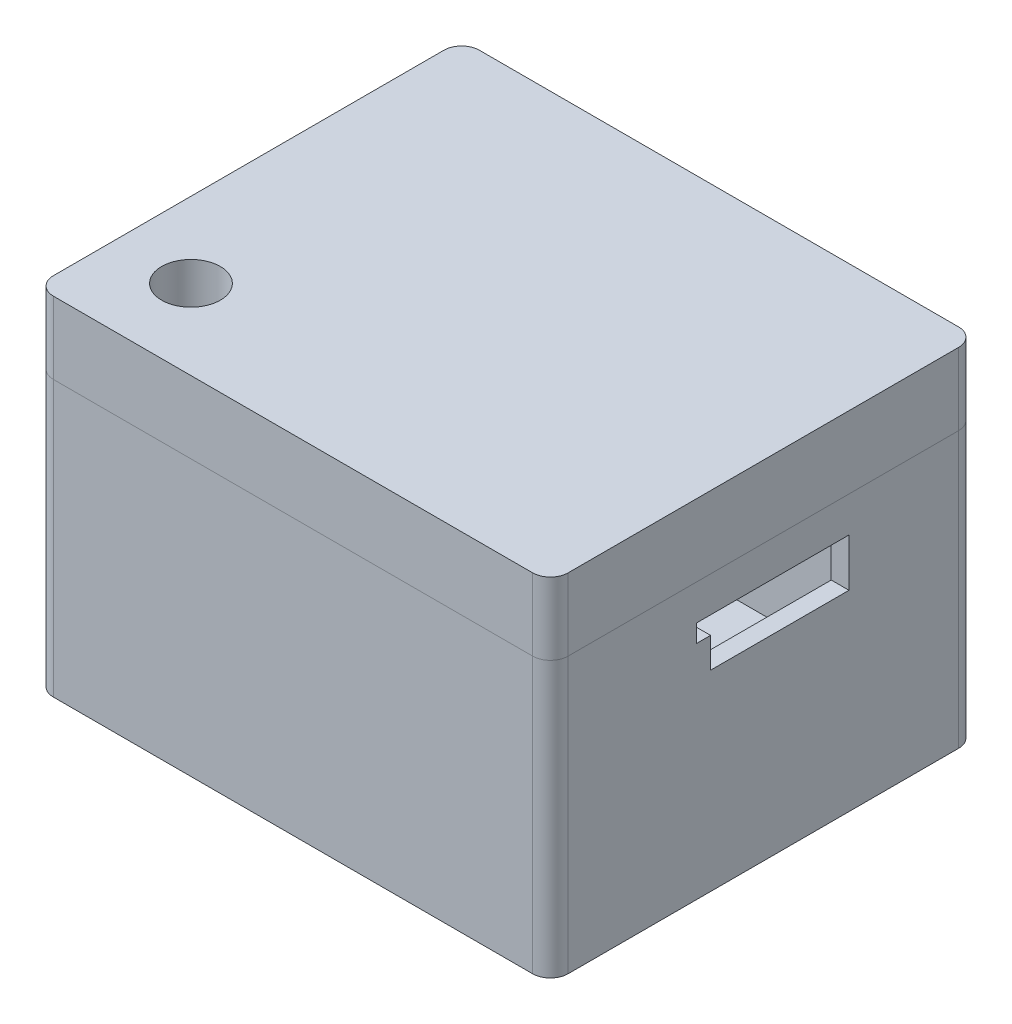
SolidWorks part; units mm, degrees
note: The reader was unsure of these and kept them because the rebuilt part matched: shared geometry of "Sketch5<3>", "Sketch5<4>", "Sketch3<3>".
ref_plane "Front Plane" through (0, 0, 0) normal (0, 0, 1) x (1, 0, 0)
ref_plane "Top Plane" through (0, 0, 0) normal (0, 1, 0) x (1, 0, 0)
ref_plane "Right Plane" through (0, 0, 0) normal (1, 0, 0) x (0, 0, -1)
sketch "Sketch1" plane through (0, 0, 0) normal (0, 1, 0) x (1, 0, 0)
  line L0 (1, 2) -> (1, 22)
  line L1 (1, 0) -> (28, 0)
  line L2 (0, 1) -> (0, 23)
  line L3 (1, 24) -> (28, 24)
  line L4 (29, 1) -> (29, 23)
  line L5 (2, 23) -> (27, 23)
  line L6 (28, 2) -> (28, 22)
  line L7 (2, 1) -> (27, 1)
  line L8 (0, 0) -> (0, 24) construction
  line L9 (0, 24) -> (29, 24) construction
  line L10 (1, 1) -> (1, 23) construction
  line L11 (1, 23) -> (28, 23) construction
  line L12 (28, 1) -> (28, 23) construction
  line L13 (29, 0) -> (29, 24) construction
  line L14 (1, 1) -> (28, 1) construction
  line L15 (0, 0) -> (29, 0) construction
  arc A0 (0, 23) -> (1, 24) centre (1, 23) cw
  arc A1 (1, 22) -> (2, 23) centre (2, 22) cw
  arc A2 (27, 23) -> (28, 22) centre (27, 22) cw
  arc A3 (28, 24) -> (29, 23) centre (28, 23) cw
  arc A4 (28, 2) -> (27, 1) centre (27, 2) cw
  arc A5 (28, 0) -> (29, 1) centre (28, 1) ccw
  arc A6 (1, 2) -> (2, 1) centre (2, 2) ccw
  arc A7 (1, 0) -> (0, 1) centre (1, 1) cw
  point P33 (0, 0)
  dimension "D4" = 1
  dimension "D2" = 29
  dimension "D3" = 24
  dimension "D1" = 1
extrude "Boss-Extrude1" add sketch "Sketch1" along normal blind 15.5 contours A7 L1 A5 L4 A3 L3 A0 L2 A6 L0 A1 L5 A2 L6 A4 L7 | L0 A6 L7 A4 L6 A2 L5 A1
sketch "Sketch2" plane through (0, 15.5, 0) normal (0, 1, 0) x (1, 0, 0)
  line L0 (1, 2) -> (1, 22) construction
  line L1 (2, 1) -> (27, 1) construction
  line L2 (2, 23) -> (27, 23) construction
  line L3 (28, 2) -> (28, 22) construction
  line L4 (1, 2) -> (1, 22)
  line L5 (2, 1) -> (27, 1)
  line L6 (2, 23) -> (27, 23)
  line L7 (28, 2) -> (28, 22)
  arc A0 (1, 2) -> (2, 1) centre (2, 2) ccw construction
  arc A1 (2, 23) -> (1, 22) centre (2, 22) ccw construction
  arc A2 (28, 22) -> (27, 23) centre (27, 22) ccw construction
  arc A3 (27, 1) -> (28, 2) centre (27, 2) ccw construction
  arc A4 (1, 2) -> (2, 1) centre (2, 2) ccw
  arc A5 (2, 23) -> (1, 22) centre (2, 22) ccw
  arc A6 (28, 22) -> (27, 23) centre (27, 22) ccw
  arc A7 (27, 1) -> (28, 2) centre (27, 2) ccw
extrude "Cut-Extrude1" cut sketch "Sketch2" against normal blind 14.5
sketch "Sketch4" plane through (29, 0, 0) normal (1, 0, 0) x (0, 0, -1)
  line L0 (8.225, 13.5) -> (16.825, 13.5)
  line L1 (16.825, 13.5) -> (16.825, 10.8)
  line L2 (16.825, 10.8) -> (9.025, 10.8)
  line L3 (9.025, 10.8) -> (9.025, 12.5)
  line L4 (9.025, 12.5) -> (8.225, 12.5)
  line L5 (8.225, 12.5) -> (8.225, 13.5)
  line L6 (3.2034, 8) -> (20.1236, 8) construction
  line L7 (2.9871, 6.8) -> (20.1236, 6.8) construction
  line L8 (5.9439, 1) -> (-49994.0561, 1) construction
  line L9 (12.925, 8) -> (12.925, 50008) construction
  line L10 (1.375, 5.7556) -> (22.625, 5.7556) construction
  line L11 (1, 0) -> (23, 0) construction
  line L12 (1, 0) -> (23, 0) construction
  line L13 (12, 0) -> (12, 50000) construction
  point P15 (12.925, 10.8)
  point P20 (12, 0)
  point P23 (12, 5.7556)
  dimension "D1" = 7.8
  dimension "D2" = 2.7
  dimension "D3" = 8.6
  dimension "D4" = 1
  dimension "D5" = 2.8
  dimension "D6" = 1.2
  dimension "D7" = 5.8
  dimension "D8" = 1
  dimension "D9" = 21.25
  dimension "D10" = 9.7
extrude "Cut-Extrude3" cut sketch "Sketch4" against normal up to next
sketch "Sketch5" plane through (0, 15.5, 0) normal (0, 1, 0) x (1, 0, 0)
  line L0 (1.5, 22) -> (1.5, 2)
  line L1 (2, 1.5) -> (27, 1.5)
  line L2 (27.5, 2) -> (27.5, 22)
  line L3 (27, 22.5) -> (2, 22.5)
  line L4 (1, 0) -> (28, 0)
  line L5 (29, 1) -> (29, 23)
  line L6 (28, 24) -> (1, 24)
  line L7 (0, 23) -> (0, 1)
  line L8 (1, 0) -> (28, 0)
  line L9 (29, 1) -> (29, 23)
  line L10 (28, 24) -> (1, 24)
  line L11 (0, 23) -> (0, 1)
  line L12 (2, 1) -> (27, 1)
  line L13 (28, 2) -> (28, 22)
  line L14 (27, 23) -> (2, 23)
  line L15 (1, 22) -> (1, 2)
  line L16 (2, 1) -> (27, 1)
  line L17 (28, 2) -> (28, 22)
  line L18 (27, 23) -> (2, 23)
  line L19 (1, 22) -> (1, 2)
  arc A0 (1.5, 2) -> (2, 1.5) centre (2, 2) ccw
  arc A1 (27, 1.5) -> (27.5, 2) centre (27, 2) ccw
  arc A2 (27.5, 22) -> (27, 22.5) centre (27, 22) ccw
  arc A3 (2, 22.5) -> (1.5, 22) centre (2, 22) ccw
  arc A4 (0, 1) -> (1, 0) centre (1, 1) ccw
  arc A5 (28, 0) -> (29, 1) centre (28, 1) ccw
  arc A6 (29, 23) -> (28, 24) centre (28, 23) ccw
  arc A7 (1, 24) -> (0, 23) centre (1, 23) ccw
  arc A8 (0, 1) -> (1, 0) centre (1, 1) ccw
  arc A9 (28, 0) -> (29, 1) centre (28, 1) ccw
  arc A10 (29, 23) -> (28, 24) centre (28, 23) ccw
  arc A11 (1, 24) -> (0, 23) centre (1, 23) ccw
  arc A12 (1, 2) -> (2, 1) centre (2, 2) ccw
  arc A13 (27, 1) -> (28, 2) centre (27, 2) ccw
  arc A14 (28, 22) -> (27, 23) centre (27, 22) ccw
  arc A15 (2, 23) -> (1, 22) centre (2, 22) ccw
  arc A16 (1, 2) -> (2, 1) centre (2, 2) ccw
  arc A17 (27, 1) -> (28, 2) centre (27, 2) ccw
  arc A18 (28, 22) -> (27, 23) centre (27, 22) ccw
  arc A19 (2, 23) -> (1, 22) centre (2, 22) ccw
  line M21 (0, 23) -> (0, 1)
  arc M24 (1, 22) -> (2, 23) centre (2, 22) cw
  line M25 (2, 23) -> (27, 23)
  arc M26 (27, 23) -> (28, 22) centre (27, 22) cw
  line M27 (28, 22) -> (28, 2)
  arc M28 (28, 2) -> (27, 1) centre (27, 2) cw
  line M29 (27, 1) -> (2, 1)
  arc M30 (2, 1) -> (1, 2) centre (2, 2) cw
  line M31 (1, 2) -> (1, 22)
  arc M34 (0, 1) -> (1, 0) centre (1, 1) ccw
  line M35 (1, 0) -> (28, 0)
  arc M36 (28, 0) -> (29, 1) centre (28, 1) ccw
  line M37 (29, 1) -> (29, 23)
  arc M38 (29, 23) -> (28, 24) centre (28, 23) ccw
  line M39 (28, 24) -> (1, 24)
  arc M40 (1, 24) -> (0, 23) centre (1, 23) ccw
  dimension "D1" = 0
  dimension "D2" = 0
  dimension "D3" = 0.5
extrude "Boss-Extrude2" add sketch "Sketch5" along normal blind 4.064 separate body contours A3 L3 A2 L2 A1 L1 A0 L0 M30 M29 M28 M27 M26 M25 M24 M31 | L3 A3 L0 A0 L1 A1 L2 A2 | M21 M34 M35 M36 M37 M38 M39 M40 M29 M30 M31 M24 M25 M26 M27 M28 | L19 A16 L16 A17 L17 A18 L18 A19
extrude "Cut-Extrude4" cut sketch "Sketch5<3>" along normal blind 3.048 contours L3 A3 L0 A0 L1 A1 L2 A2
sketch "Sketch5<3>" plane through (0, 15.5, 0) normal (0, 1, 0) x (1, 0, 0) same geometry as "Sketch5"
extrude "Boss-Extrude3" add sketch "Sketch5<4>" against normal blind 1 contours A3 L3 A2 L2 A1 L1 A0 L0 M30 M29 M28 M27 M26 M25 M24 M31
sketch "Sketch5<4>" plane through (0, 15.5, 0) normal (0, 1, 0) x (1, 0, 0) same geometry as "Sketch5"
sketch "Sketch3" plane through (0, 0, 0) normal (1, 0, 0) x (0, 0, -1)
  line L0 (2, 15.5) -> (22, 15.5) construction
  line L1 (15.159, 15.5) -> (10.841, 15.5) construction
  line L2 (15.159, 15.5) -> (15.159, 8.388)
  line L3 (15.159, 8.388) -> (10.841, 8.388) construction
  line L4 (10.841, 15.5) -> (10.841, 8.388) construction
  line L5 (2, 15.5) -> (22, 15.5) construction
  line L6 (1, 0) -> (23, 0) construction
  line L7 (1, 0) -> (23, 0) construction
  line L8 (12, 0) -> (12, 2.1392) construction
  line L9 (13, 8.388) -> (13, 15.5) construction
  line L10 (17.009, 15.5) -> (17.009, 13.65)
  line L11 (17.009, 13.65) -> (13.309, 13.65)
  line L12 (13.309, 13.65) -> (13.309, 15.5)
  circle A0 centre (15.159, 15.5) radius 1.85
  circle A1 centre (10.841, 8.388) radius 1.85
  point P13 (12, 0)
  dimension "D1" = 3.7
  dimension "D2" = 4.318
  dimension "D3" = 7.112
  dimension "D4" = 1
extrude "Cut-Extrude2" cut sketch "Sketch3" along normal up to surface (1.5 mm away)
extrude "Cut-Extrude5" cut sketch "Sketch3<3>" along normal up to next contours A0 L11 L10 | A0 L12 L11
sketch "Sketch3<3>" plane through (0, 0, 0) normal (1, 0, 0) x (0, 0, -1) same geometry as "Sketch3"
sketch "Sketch6" plane through (0, 1, 0) normal (0, 1, 0) x (1, 0, 0)
  line L0 (1, 8) -> (7.5, 8)
  line L1 (7.5, 8) -> (7.5, 1)
  line L2 (4.25, 8) -> (4.25, 1) construction
  line L3 (7.5, 4.5) -> (1, 4.5) construction
  line L4 (2, 1) -> (27, 1)
  line L5 (28, 2) -> (28, 22)
  line L6 (27, 23) -> (2, 23)
  line L7 (1, 22) -> (1, 2)
  line L8 (2, 1) -> (7.5, 1)
  line L11 (1, 8) -> (1, 2)
  circle A0 centre (4.25, 4.5) radius 1.4
  arc A4 (1, 2) -> (2, 1) centre (2, 2) ccw
  arc A5 (27, 1) -> (28, 2) centre (27, 2) ccw
  arc A6 (28, 22) -> (27, 23) centre (27, 22) ccw
  arc A7 (2, 23) -> (1, 22) centre (2, 22) ccw
  arc A8 (1, 2) -> (2, 1) centre (2, 2) ccw
  dimension "D4" = 2.8
  dimension "D2" = 6.5
  dimension "D3" = 7
  dimension "D1" = 0
extrude "Boss-Extrude4" add sketch "Sketch6" along normal blind 4
fillet "Fillet1" radius 1 3 edges at (7.5, 3, -1) (1, 3, -8) (7.5, 3, -8)
sketch "Sketch7" plane through (0, 5, 0) normal (0, 1, 0) x (1, 0, 0)
  line L4 (7.5, 8) -> (1, 8)
  line L5 (7.5, 1) -> (7.5, 8)
  line L6 (2, 1) -> (7.5, 1)
  line L7 (1, 8) -> (1, 2)
  line L8 (7.5, 8) -> (1, 8)
  line L9 (7.5, 1) -> (7.5, 8)
  line L10 (2, 1) -> (7.5, 1)
  line L11 (1, 8) -> (1, 2)
  circle A0 centre (4.25, 4.5) radius 1.65
  arc A1 (1, 2) -> (2, 1) centre (2, 2) ccw
  arc A2 (1, 2) -> (2, 1) centre (2, 2) ccw
  circle A3 centre (4.25, 4.5) radius 1.4
  circle A4 centre (4.25, 4.5) radius 1.4 construction
  dimension "D3" = 3.3
  dimension "D1" = 0
  dimension "D2" = 0
extrude "Boss-Extrude5" add sketch "Sketch7" along normal up to body
sketch "Sketch8" plane through (0, 5, 0) normal (0, -1, 0) x (1, 0, 0)
  circle A0 centre (4.25, -4.5) radius 1.65 construction
  circle A1 centre (4.25, -4.5) radius 1.65
extrude "Cut-Extrude6" cut sketch "Sketch8" against normal through all
fillet "Fillet2" radius 1 3 edges at (1.5, 16.524, -8) (7.5, 11.774, -8) (7.5, 16.524, -1.5)
fillet "Fillet3" radius 0.25 2 edges at (1, 9.75, -8) (7.5, 9.75, -1)
